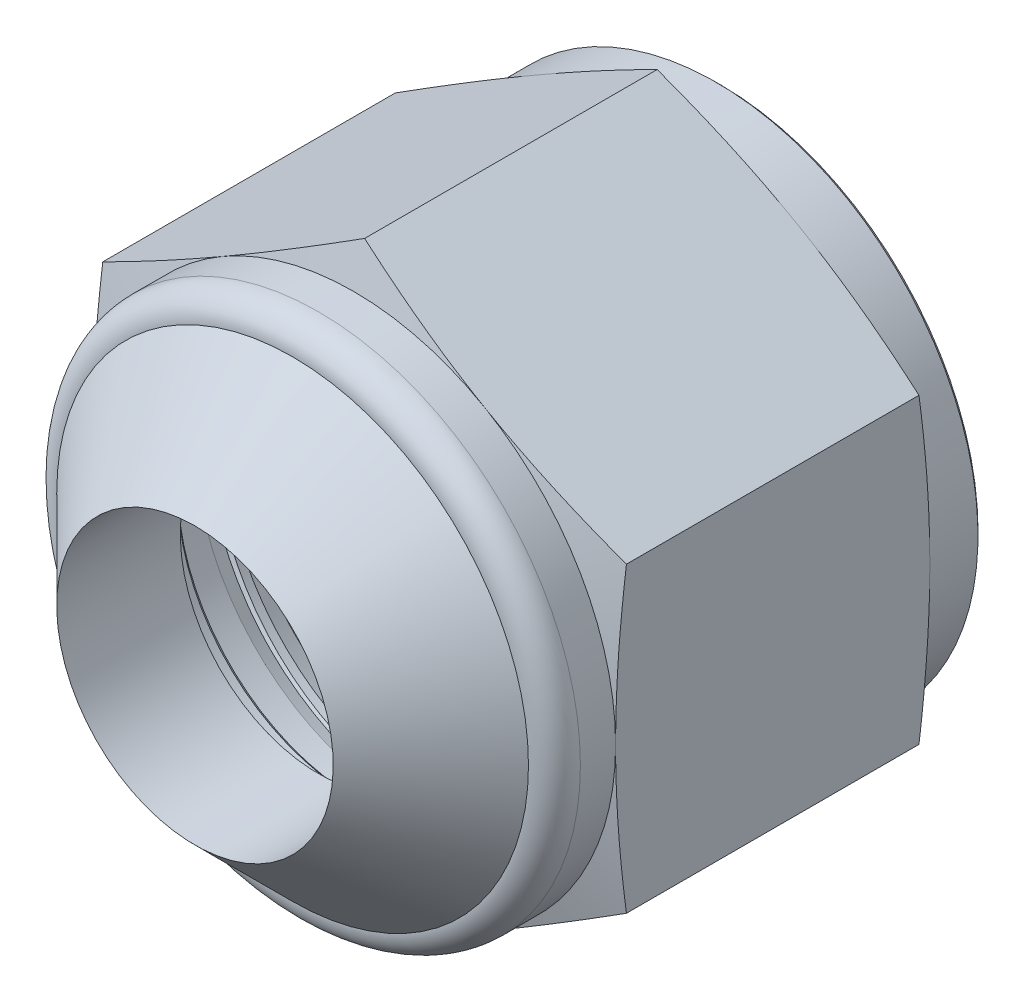
SolidWorks part; units mm, degrees
material "AISI 316 Stainless Steel Sheet (SS)"
ref_plane "Front Plane" through (0, 0, 0) normal (0, 0, 1) x (1, 0, 0)
ref_plane "Top Plane" through (0, 0, 0) normal (0, 1, 0) x (1, 0, 0)
ref_plane "Right Plane" through (0, 0, 0) normal (1, 0, 0) x (0, 0, -1)
sketch "Sketch0" plane through (0, 0, 0) normal (1, 0, 0) x (0, 0, -1)
  line L0 (0, 0) -> (-25.9334, 0) construction
  line L4 (-25.9334, 15.875) -> (-25.9334, -15.875) construction
  line L5 (-25.9334, 15.875) -> (-25.9334, -15.875) construction
  line L6 (-25.9334, 10.5918) -> (-25.9334, -10.5918) construction
  line L7 (0, 13.4937) -> (0, -13.4937) construction
  line L8 (0, -13.4874) -> (0, 13.4874) construction
  line L9 (0, -13.4874) -> (-2.1167, -13.4874) construction
  point P16 (-22.0472, 0)
  point P20 (-19.1262, 0)
  point P22 (-13.6398, 0)
  point P34 (-3.175, 0)
  point P35 (-22.225, 0)
  dimension "P" = 31.75
  dimension "M" = 25.9334
  dimension "L" = 22.0472
  dimension "S" = 19.1262
  dimension "Q" = 13.6398
  dimension "A" = 21.1836
  dimension "C" = 31.75
  dimension "T" = 26.9875
  dimension "B" = 3.175
  dimension "J" = 19.05
  dimension "H" = 26.9748
  dimension "Pitch" = 2.1167
sketch "Sketch1" plane through (0, 0, 0) normal (0, 0, 1) x (1, 0, 0)
  line L1 (0, 18.3309) -> (-15.875, 9.1654)
  line L2 (-15.875, 9.1654) -> (-15.875, -9.1654)
  line L3 (-15.875, -9.1654) -> (0, -18.3309)
  line L4 (0, -18.3309) -> (15.875, -9.1654)
  line L5 (15.875, -9.1654) -> (15.875, 9.1654)
  line L6 (15.875, 9.1654) -> (0, 18.3309)
  circle A0 centre (0, 0) radius 15.875 construction
extrude "Boss-Extrude1" add sketch "Sketch1" along normal up to vertex (25.9334 mm away) up to point (0, 0, 25.9334)
sketch "Sketch2" plane through (0, 0, 0) normal (1, 0, 0) x (0, 0, -1)
  line L0 (-25.9334, 20.7867) -> (-25.9334, 15.875)
  line L1 (-25.9334, 15.875) -> (-22.225, 15.875)
  line L2 (-22.225, 15.875) -> (-21.567, 18.3309)
  line L3 (-25.9334, 18.3309) -> (0, 18.3309) construction
  line L4 (-21.567, 18.3309) -> (-3.833, 18.3309)
  line L5 (-3.833, 18.3309) -> (-3.175, 15.875)
  line L6 (-3.175, 15.875) -> (-22.225, 15.875) construction
  line L7 (-3.175, 15.875) -> (0, 15.875)
  line L8 (0, 15.875) -> (0, 20.7867)
  line L9 (-25.9334, 20.7867) -> (0, 20.7867)
  line L10 (-3.175, 15.875) -> (-3.175, 0) construction
  line L11 (-22.225, 15.875) -> (-22.225, 0) construction
  line L12 (-25.9334, 10.5918) -> (-25.9334, 0)
  line L13 (-25.9334, 15.875) -> (-25.9334, -15.875) construction
  line L14 (-25.9334, 0) -> (0, 0)
  line L15 (0, 0) -> (0, 12.7204)
  line L16 (-22.0472, 10.5918) -> (-22.0472, 0) construction
  line L17 (-22.0472, 10.5918) -> (-22.0472, 12.4664)
  line L18 (-21.7932, 12.7204) -> (0, 12.7204)
  line L19 (-22.0472, 10.5918) -> (-25.9334, 10.5918)
  line L23 (-19.1262, 0) -> (-19.1262, 12.7204) construction
  arc A0 (-22.0472, 12.4664) -> (-21.7932, 12.7204) centre (-21.7932, 12.4664) cw
  dimension "D3" = 0.254
  dimension "D1" = 15
  dimension "D2" = 15
  dimension "D4" = 0.7733
revolve "Cut-Revolve1" cut sketch "Sketch2" angle 360 about L0 other way angle 360
sketch "Sketch3" plane through (0, 0, 0) normal (0, 0, -1) x (-1, 0, 0)
  circle A0 centre (0, 0) radius 12.7204
  circle A1 centre (0, 0) radius 12.7204 construction
  point P3 (0, 12.7204)
fillet "Fillet1" radius 1.5748 1 edges at (15.875, 0, 25.9334)
chamfer "Chamfer1" distance 0.254 angle 45 1 edges at (15.875, 0, 0)
chamfer "Chamfer2" distance 0.254 angle 45 2 edges at (0, 10.5918, 22.0472) (0, 10.5918, 25.9334)
ref_axis "Centre Axis 1" through (0, 0, 25.2505) along (0, 0, -1)
curve "Helix/Spiral1" pitch 2.1167 height 21.2429 radius 12.7204 centre (0, 0, 0) axis (0, 0, 1) start towards (0, 1, 0) parameters "Pitch"=2.1167
sketch "Sketch4" plane through (0, 0, 0) normal (1, 0, 0) x (0, 0, -1)
  line L0 (-0.248, 12.2908) -> (1.8686, 12.2908) construction
  line L1 (1.8686, 12.2908) -> (0.8103, 14.1239) construction
  line L2 (0.8103, 14.1239) -> (-0.248, 12.2908) construction
  line L3 (0.7111, 13.952) -> (0.9095, 13.952) construction
  line L4 (0.8103, 12.7204) -> (0.8103, 12.2908) construction
  line L5 (0, 12.7204) -> (1.6206, 12.7204) construction
  line L6 (0.8103, 14.1239) -> (0.8103, 13.952) construction
  line L7 (0.7111, 13.952) -> (-0.124, 12.5056)
  line L8 (-0.124, 12.5056) -> (1.7446, 12.5056)
  line L9 (1.7446, 12.5056) -> (0.9095, 13.952)
  arc A0 (0.9095, 13.952) -> (0.7111, 13.952) centre (0.8103, 13.8947) ccw
  point P6 (0.8103, 12.5056)
  dimension "D1" = 2.1167
  dimension "D2" = 1.8331
  dimension "D4" = 0.4296
  dimension "D3" = 0.1719
  dimension "D5" = 1.2316
sweep "Cut-Sweep1" cut profiles "Sketch4" path "Helix/Spiral1" align with end faces yes
sketch "Sketch5" plane through (0, 0, 0) normal (0, 0, -1) x (-1, 0, 0)
  circle A0 centre (0, 0) radius 13.4874
extrude "Cut-Extrude1" cut sketch "Sketch5" against normal through all draft 45
sketch "Sketch6" plane through (0, 0, 0) normal (1, 0, 0) x (0, 0, -1)
  line L0 (-22.0472, 14.1239) -> (-13.6398, 14.1239)
  line L1 (-13.6398, 14.1239) -> (-19.1262, 12.7204)
  line L2 (-19.1262, 12.7204) -> (-22.0472, 12.7204)
  line L3 (-22.0472, 12.7204) -> (-22.0472, 14.1239)
  line L4 (-13.6398, 0) -> (-13.6398, 14.1239) construction
  line L5 (-19.1262, 0) -> (-19.1262, 12.7204) construction
  line L7 (-22.0472, 12.7204) -> (-22.0472, 0) construction
  line L8 (-21.7932, 12.7204) -> (0, 12.7204) construction
  line L9 (-13.6398, 14.1239) -> (0.8103, 14.1239) construction
revolve "Revolve1" add sketch "Sketch6" angle 360 about L0
sketch "SketchX" plane through (0, 0, 0) normal (0, 0, -1) x (-1, 0, 0)
  line L0 (0, 0) -> (-6.7437, 11.6804) construction
  line L1 (-7.9375, 13.7482) -> (-15.875, 9.1654) construction
  circle A0 centre (0, 0) radius 13.4874 construction
sketch "Sketch9" plane through (0, 0, 0) normal (1, 0, 0) x (0, 0, -1)
  line L0 (-24.3586, 15.875) -> (-24.3586, 0) construction
  line L1 (-24.3586, -15.875) -> (-24.3586, 15.875) construction
  line L2 (-24.3586, 0) -> (-39.3446, 0) construction
  line L3 (-39.3446, 0) -> (-39.3446, 8.382) construction
  line L4 (-39.3446, 8.382) -> (-24.3586, 8.382) construction
  line L5 (-24.3586, 15.875) -> (-24.3586, 8.382)
  line L6 (-24.3586, 8.382) -> (-31.8516, 8.382)
  line L7 (-31.8516, 8.382) -> (-24.3586, 15.875)
  dimension "D1" = 8.382
  dimension "D2" = 45
revolve "Revolve2" add sketch "Sketch9" angle 360 about L2
equation "\"D3@Helix/Spiral1\"= \"Pitch@Sketch0\" + \"S@Sketch0\""
equation "\"D1@Sketch4\"=\"Pitch@Sketch0\""
equation "\"Pitch@Helix/Spiral1\"=\"Pitch@Sketch0\""
